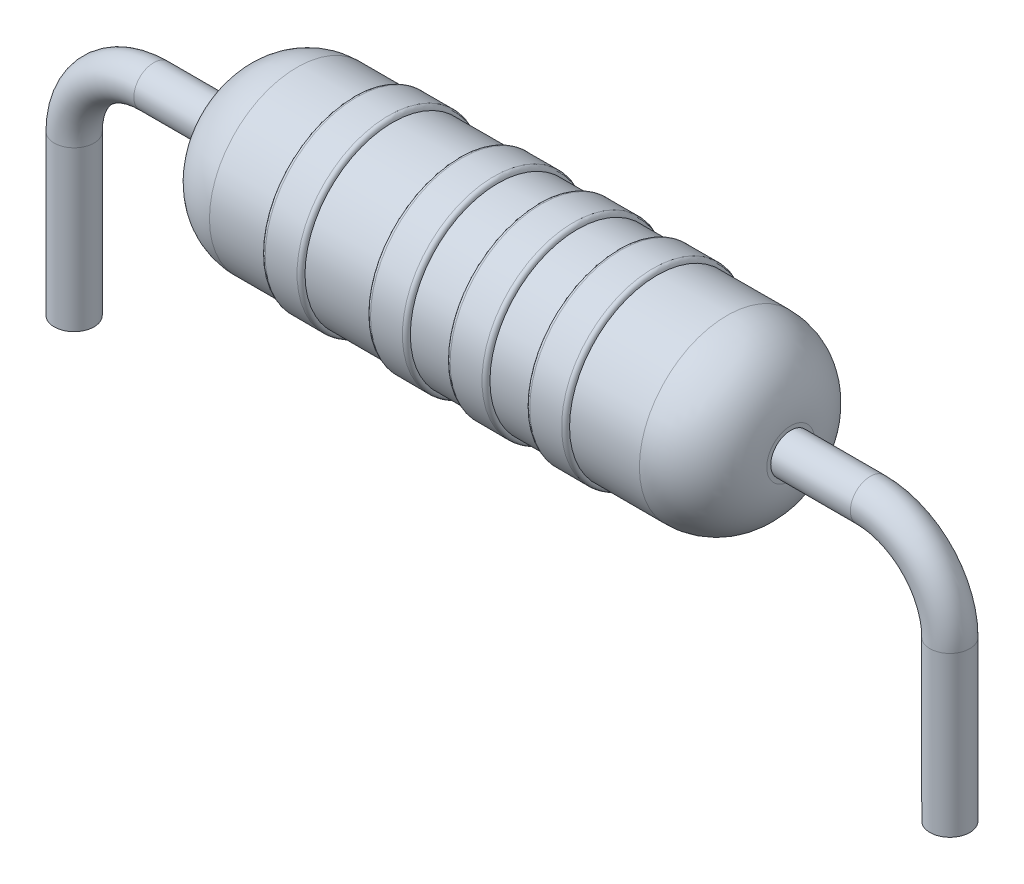
SolidWorks part; units mm, degrees
ref_plane "Face" through (0, 0, 0) normal (0, 0, 1) x (1, 0, 0)
ref_plane "Dessus" through (0, 0, 0) normal (0, 1, 0) x (1, 0, 0)
ref_plane "Droite" through (0, 0, 0) normal (1, 0, 0) x (0, 0, -1)
sketch "Esquisse1" plane through (0, 0, 0) normal (0, 0, 1) x (1, 0, 0)
  line L0 (-54.2687, 0) -> (62.1733, 0) construction
  line L1 (-48.4922, 1.1) -> (45.7559, 1.1) construction
  line L2 (-3.5, -1.6411) -> (-3.5, 4.3175) construction
  line L3 (0, -1.0268) -> (0, 4.1947) construction
  line L4 (3.5, 3.6009) -> (3.5, -1.9687) construction
  line L5 (-3.5, 0) -> (-3.5, 0.3)
  line L6 (-2.7, 1.1) -> (2.7, 1.1)
  line L7 (3.5, 0.3) -> (3.5, 0)
  line L8 (3.5, 0) -> (-3.5, 0)
  arc A0 (-2.7, 1.1) -> (-3.5, 0.3) centre (-2.7, 0.3) ccw
  arc A1 (3.5, 0.3) -> (2.7, 1.1) centre (2.7, 0.3) ccw
revolve "Base-Révolution" add sketch "Esquisse1" angle 360 about L0
sketch "Esquisse2" plane through (0, 0, 0) normal (0, 0, 1) x (1, 0, 0)
  line L0 (-3.3896, 1.15) -> (3.161, 1.15) construction
  line L1 (-2, 1.3889) -> (-2, -0.1179) construction
  line L2 (-1.5, 1.4925) -> (-1.5, -0.2136) construction
  line L3 (4.3262, 0) -> (-3.8651, 0) construction
  line L4 (1.323, 0) -> (1.823, 0)
  line L5 (0.323, 0) -> (0.823, 0)
  line L6 (-0.677, 1.15) -> (-0.677, 0)
  line L7 (0.323, 1.15) -> (0.323, 0)
  line L8 (1.323, 1.15) -> (1.323, 0)
  line L9 (-0.177, 1.15) -> (-0.177, 0)
  line L10 (0.823, 1.15) -> (0.823, 0)
  line L11 (1.823, 1.15) -> (1.823, 0)
  line L12 (-0.677, 0) -> (-0.177, 0)
  line L13 (-0.677, 1.15) -> (-0.177, 1.15)
  line L14 (0.323, 1.15) -> (0.823, 1.15)
  line L15 (1.323, 1.15) -> (1.823, 1.15)
  line L16 (-2, 1.15) -> (-1.5, 1.15)
  line L17 (-1.5, 1.15) -> (-1.5, 0)
  line L18 (-1.5, 0) -> (-2, 0)
  line L19 (-2, 0) -> (-2, 1.15)
revolve "Boss.-Révol.1" add sketch "Esquisse2" angle 360 about L3
fillet "Congé1" radius 0.05 8 edges at (-2, 0, -1.15) (-1.5, 0, -1.15) (-0.677, 0, -1.15) (-0.177, 0, -1.15) (0.323, 0, -1.15) (0.823, 0, -1.15) (1.323, 0, -1.15) (1.823, 0, -1.15)
sketch "Esquisse3" plane through (-3.5, 0, 0) normal (-1, 0, 0) x (0, 0, 1)
  circle A0 centre (0, 0) radius 0.25
sketch "Esquisse4" plane through (0, 0, 0) normal (0, 0, 1) x (1, 0, 0)
  line L0 (-3.1075, 0) -> (-5.8186, 0) construction
  line L1 (0, -2.524) -> (0, 3.2043) construction
  line L2 (-5.9326, -3) -> (3.6667, -3) construction
  line L3 (-5.5, 1.6795) -> (-5.5, -3.4934) construction
  line L4 (-3.5, 0) -> (-4.5, 0)
  line L5 (-5.5, -1) -> (-5.5, -3)
  arc A0 (-4.5, 0) -> (-5.5, -1) centre (-4.5, -1) ccw
  dimension "D3" = 1
  dimension "D1" = 3
  dimension "D2" = 5.5
sweep "Balayage1" add profiles "Esquisse3" path "Esquisse4"
ref_plane "Plan1" through (0, 0, 0) normal (1, 0, 0) x (0, 0, -1)
mirror "Symétrie1" about plane through (0, 0, 0) normal (1, 0, 0) of "Balayage1"
